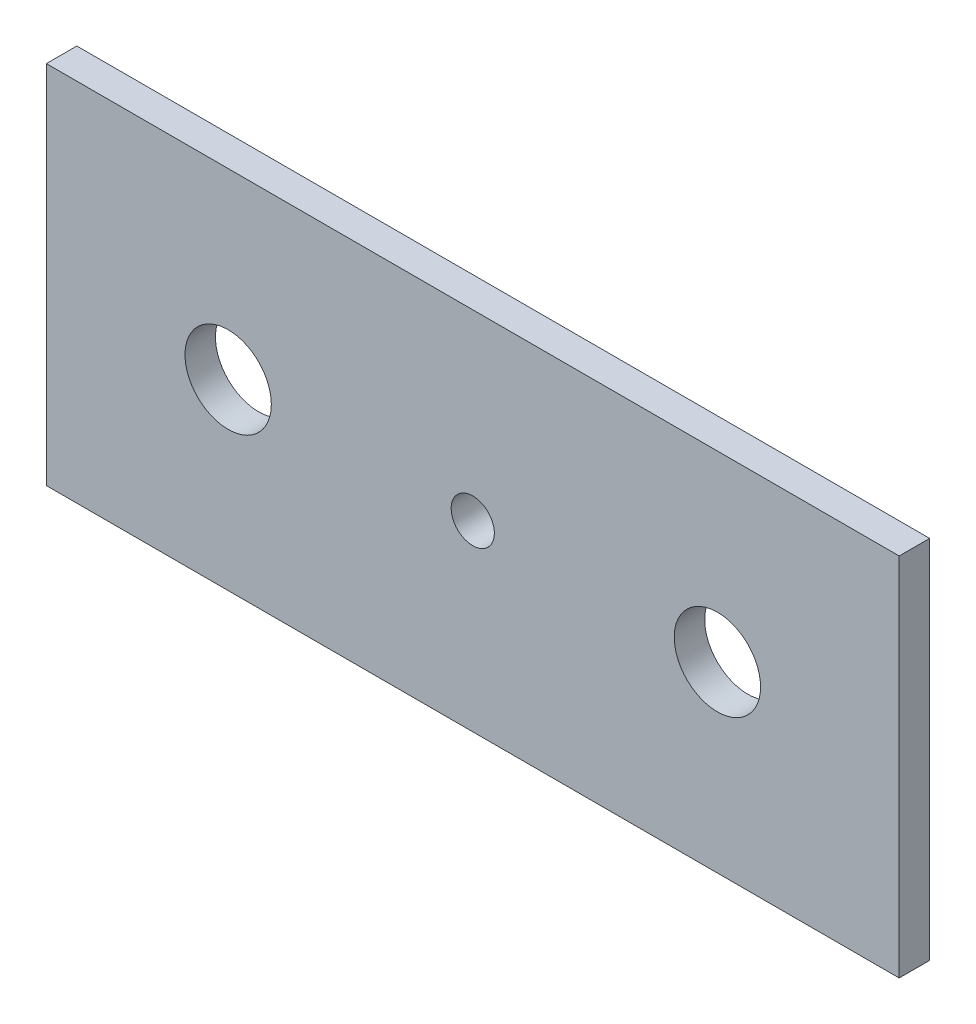
SolidWorks part; units mm, degrees
material "Plain Carbon Steel"
ref_plane "Front Plane" through (0, 0, 0) normal (0, 0, 1) x (1, 0, 0)
ref_plane "Top Plane" through (0, 0, 0) normal (0, 1, 0) x (1, 0, 0)
ref_plane "Right Plane" through (0, 0, 0) normal (1, 0, 0) x (0, 0, -1)
sketch "Sketch1" plane through (0, 0, 0) normal (0, 0, 1) x (1, 0, 0)
  line L0 (-27.5, -9.525) -> (27.5, -9.525) construction
  line L1 (44.45, -19.05) -> (-44.45, -19.05)
  line L2 (44.45, -19.05) -> (44.45, 19.05)
  line L3 (44.45, 19.05) -> (-44.45, 19.05)
  line L4 (-44.45, -19.05) -> (-44.45, 19.05)
  line L5 (27.5, 9.525) -> (-27.5, 9.525) construction
  line L6 (-27.5, -9.525) -> (27.5, -9.525) construction
  line L11 (27.5, 9.525) -> (-27.5, 9.525) construction
  arc A0 (27.5, -9.525) -> (27.5, 9.525) centre (27.5, 0) ccw construction
  arc A1 (-27.5, 9.525) -> (-27.5, -9.525) centre (-27.5, 0) ccw construction
  arc A2 (27.5, -9.525) -> (27.5, 9.525) centre (27.5, 0) ccw construction
  arc A3 (-27.5, 9.525) -> (-27.5, -9.525) centre (-27.5, 0) ccw construction
  point P0 (0, 0)
  point P6 (0, 0)
  point P7 (0, 19.05)
  point P8 (-44.45, 0)
  dimension "D1" = 19.05
  dimension "D2" = 38.1
  dimension "D3" = 88.9
extrude "Boss-Extrude1" add sketch "Sketch1" against normal blind 3.175
hole_wizard "M4 Clearance Hole1" positions "Sketch4" profile "Sketch3" hole size "M4" standard "ANSI Metric" end condition through all
sketch "Sketch4" plane through (0, 0, 0) normal (0, 0, 1) x (1, 0, 0)
  point P0 (0, 0)
sketch "Sketch3" plane through (0, 0, 0) normal (1, 0, 0) x (0, -1, 0)
  line L0 (0, 0) -> (0, 3.175)
  line L1 (0, 3.175) -> (2.25, 3.175)
  line L2 (2.25, 3.175) -> (2.25, 0)
  line L5 (2.25, 0) -> (0, 0)
  line L11 (0, -6.35) -> (0, 107.95) construction
  dimension "Thru Hole Dia." = 4.5
  dimension "Thru Hole Depth" = 3.175
hole_wizard "M8 Clearance Hole1" positions "Sketch7" profile "Sketch6" hole size "M8" standard "ANSI Metric" end condition through all
sketch "Sketch7" plane through (0, 0, 0) normal (0, 0, 1) x (1, 0, 0)
  line L0 (-25.5, 0) -> (25.5, 0) construction
  line L2 (25.5, 0) -> (-25.5, 0) construction
  point P0 (-25.5, 0)
  point P3 (25.5, 0)
  point P16 (0, 0)
sketch "Sketch6" plane through (-25.5, 0, 0) normal (1, 0, 0) x (0, -1, 0)
  line L0 (0, 0) -> (0, 3.175)
  line L1 (0, 3.175) -> (4.5, 3.175)
  line L2 (4.5, 3.175) -> (4.5, 0)
  line L5 (4.5, 0) -> (0, 0)
  line L11 (0, -6.35) -> (0, 107.95) construction
  dimension "Thru Hole Dia." = 9
  dimension "Thru Hole Depth" = 3.175
